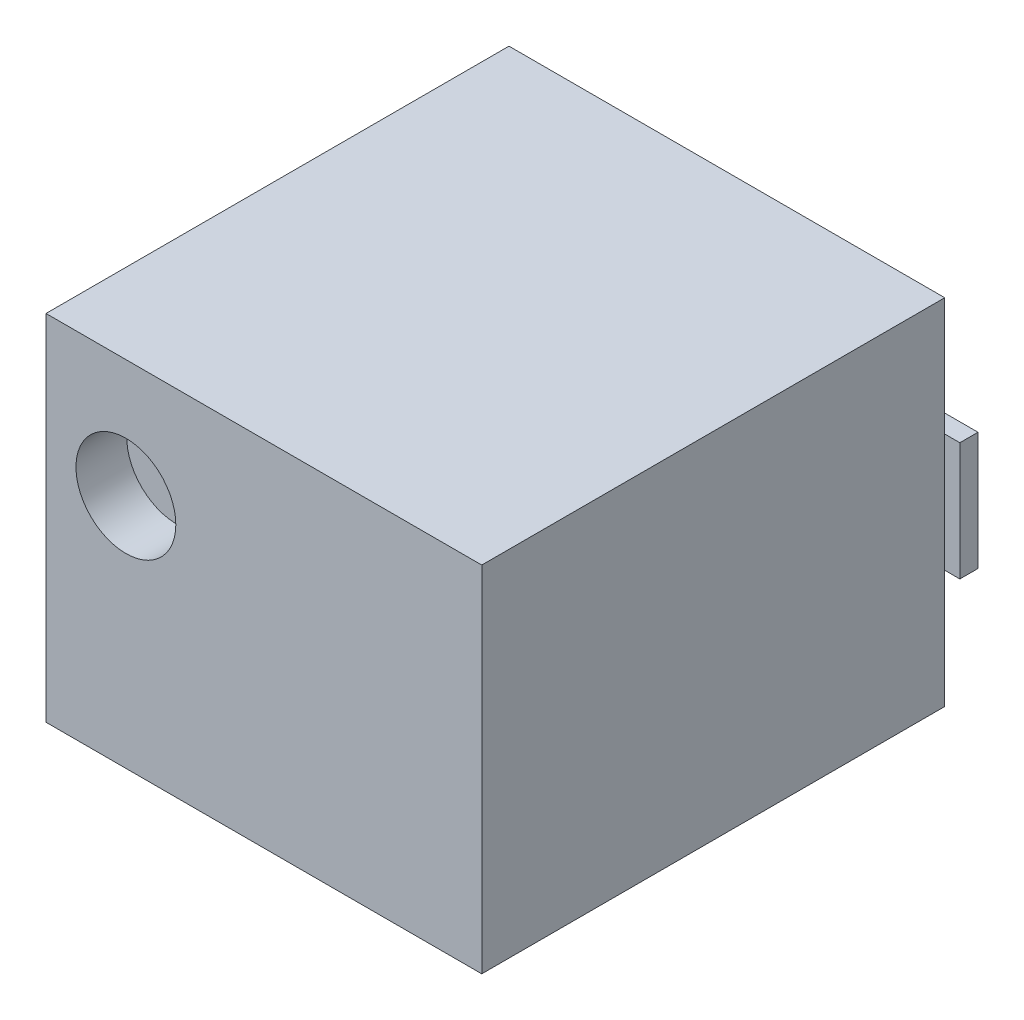
SolidWorks part; units mm, degrees
ref_plane "前视" through (0, 0, 0) normal (0, 0, 1) x (1, 0, 0)
ref_plane "上视" through (0, 0, 0) normal (0, 1, 0) x (1, 0, 0)
ref_plane "右视" through (0, 0, 0) normal (1, 0, 0) x (0, 0, -1)
sketch "草图1" plane through (0, 0, 0) normal (0, 1, 0) x (1, 0, 0)
  line L0 (0, 81.3418) -> (0, -101.3275) construction
  line L1 (-87.3375, 0) -> (113.7186, 0) construction
  line L3 (-2.4, 2.55) -> (2.4, 2.55)
  line L4 (-2.4, 2.55) -> (-2.4, -2.55)
  line L5 (-2.4, -2.55) -> (2.4, -2.55)
  line L6 (2.4, 2.55) -> (2.4, -2.55)
  dimension "D1" = 4.8
  dimension "D2" = 5.1
extrude "拉伸1" add sketch "草图1" along normal blind 1.95 and the other way blind 1.95
sketch "草图4" plane through (0, 0, 2.55) normal (0, 0, 1) x (1, 0, 0)
  line L0 (-2.4, -1.95) -> (2.4, -1.95) construction
  line L1 (0, 3.6963) -> (0, -4.2954) construction
  circle A0 centre (-1.52, 0.65) radius 0.55
  dimension "D1" = 1.1
  dimension "D2" = 2.6
  dimension "D3" = 1.52
extrude "切除-拉伸1" cut sketch "草图4" against normal blind 0.56
sketch "草图5" plane through (0, 0, -2.55) normal (0, 0, -1) x (-1, 0, 0)
  line L0 (0, 3.1322) -> (0, -3.3082) construction
  line L1 (-3.4286, 0) -> (2.8906, 0) construction
  line L2 (2.4, 1.95) -> (2.4, -1.95) construction
  line L3 (-2.5664, 0.65) -> (-1.2777, 0.65)
  line L4 (-2.5664, 0.65) -> (-2.5664, -0.65)
  line L5 (-2.5664, -0.65) -> (-1.2777, -0.65)
  line L6 (-1.2777, 0.65) -> (-1.2777, -0.65)
  line L7 (1.586, 1.6601) -> (2.6, 1.6601)
  line L8 (1.586, 1.6601) -> (1.586, 1.058)
  line L9 (1.586, 1.058) -> (2.6, 1.058)
  line L10 (2.6, 1.6601) -> (2.6, 1.058)
  line L11 (2.6, -1.6601) -> (2.6, -1.058)
  line L12 (1.586, -1.058) -> (2.6, -1.058)
  line L13 (1.586, -1.6601) -> (1.586, -1.058)
  line L14 (1.586, -1.6601) -> (2.6, -1.6601)
  dimension "D1" = 0.2
  dimension "D2" = 1.3
extrude "凸台-拉伸1" add sketch "草图5" along normal blind 0.2
